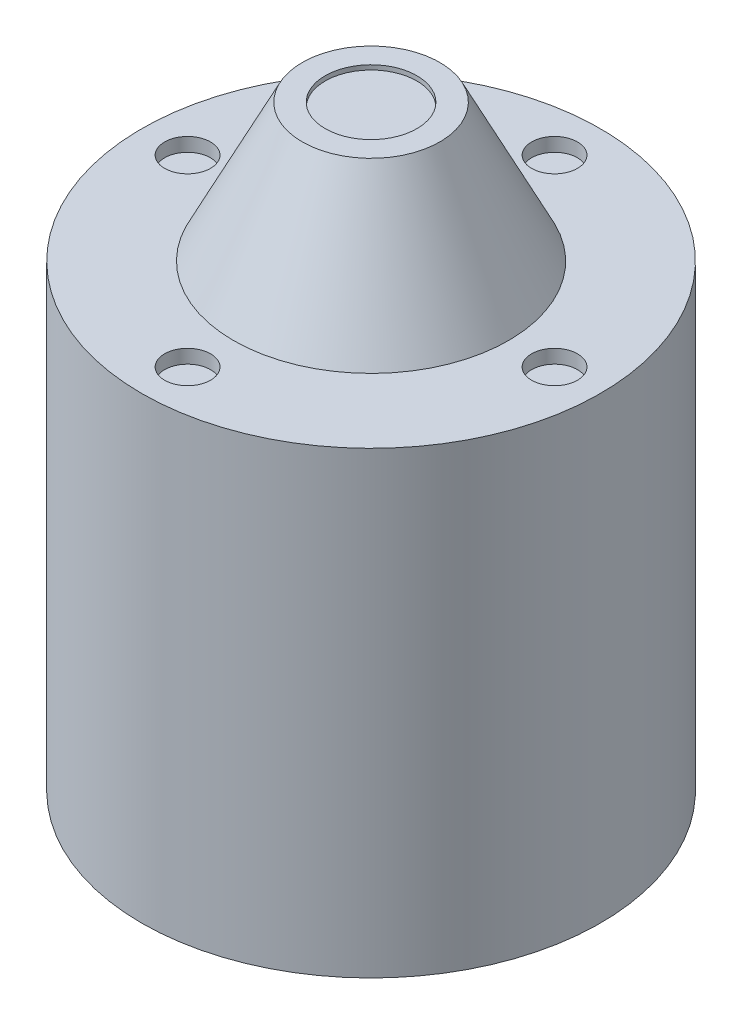
SolidWorks part; units mm, degrees
ref_plane "Front Plane" through (0, 0, 0) normal (0, 0, 1) x (1, 0, 0)
ref_plane "Top Plane" through (0, 0, 0) normal (0, 1, 0) x (1, 0, 0)
ref_plane "Right Plane" through (0, 0, 0) normal (1, 0, 0) x (0, 0, -1)
sketch "Sketch1" plane through (0, 0, 0) normal (0, 1, 0) x (1, 0, 0)
  circle A0 centre (0, 0) radius 25
  dimension "D1" = 50
extrude "Boss-Extrude1" add sketch "Sketch1" along normal blind 50
ref_plane "Plane1" through (0, 65, 0) normal (0, 1, 0) x (1, 0, 0)
sketch "Sketch3" plane through (0, 65, 0) normal (0, 1, 0) x (1, 0, 0)
  circle A0 centre (0, 0) radius 7.5
  dimension "D1" = 15
sketch "Sketch4" plane through (0, 50, 0) normal (0, 1, 0) x (1, 0, 0)
  circle A0 centre (0, 0) radius 15
  dimension "D1" = 30
loft "Loft1" add profiles "Sketch3", "Sketch4" connector at (0, 65, 7.5) connector at (0, 50, 15)
sketch "Sketch5" plane through (0, 65, 0) normal (0, 1, 0) x (1, 0, 0)
  circle A0 centre (0, 0) radius 5
  circle A1 centre (0, 0) radius 20 construction
  circle A2 centre (-20, 0) radius 2.5
  circle A3 centre (0, 20) radius 2.5
  circle A4 centre (20, 0) radius 2.5
  circle A5 centre (0, -20) radius 2.5
  point P15 (0, 0)
  dimension "D1" = 10
  dimension "D2" = 40
  dimension "D3" = 5
  dimension "D4" = 4
extrude "Cut-Extrude1" cut sketch "Sketch5" against normal blind 0.5 contours A0 region at (0, 65, 0)
extrude "Cut-Extrude2" cut sketch "Sketch5<4>" against normal blind 1.5 from surface contours A2 | A3 | A4 | A5 region at (-20, 65, 0) region at (0, 65, -20) region at (20, 65, 0) region at (0, 65, 20) starting at face at (0, 50, 25)
sketch "Sketch5<4>" plane through (0, 65, 0) normal (0, 1, 0) x (1, 0, 0) same geometry as "Sketch5"
